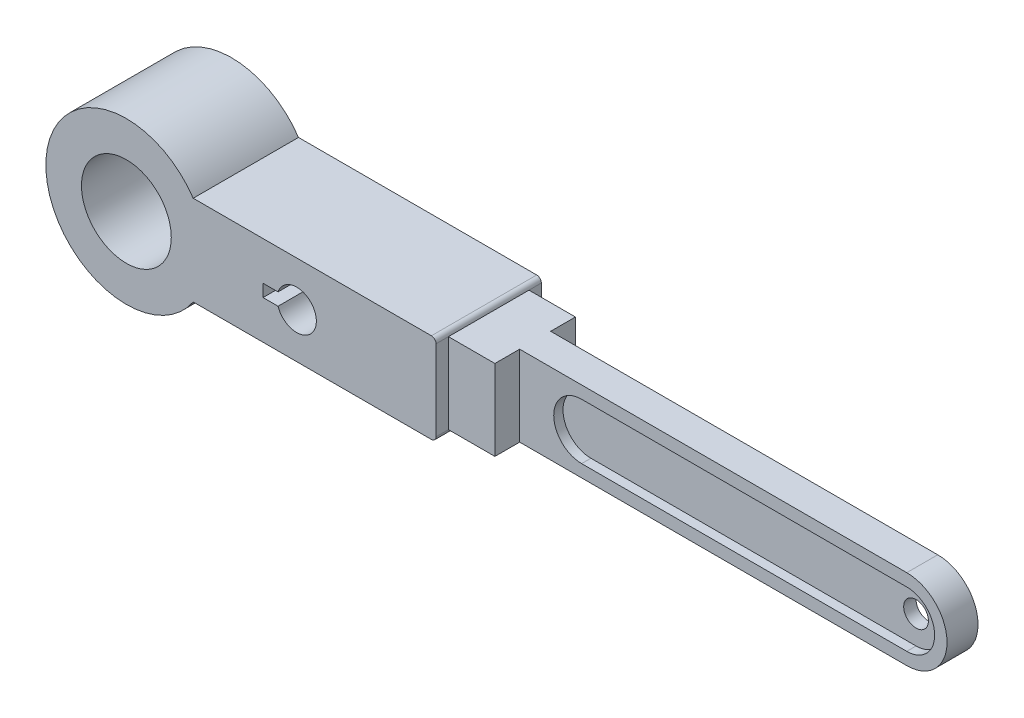
SolidWorks part; units mm, degrees
note: The reader was unsure of these and kept them because the rebuilt part matched: shared geometry of "Esboço1<4>", "Esboço1<8>", "Esboço1<9>".
ref_plane "Plano frontal" through (0, 0, 0) normal (0, 0, 1) x (1, 0, 0)
ref_plane "Plano superior" through (0, 0, 0) normal (0, 1, 0) x (1, 0, 0)
ref_plane "Plano direito" through (0, 0, 0) normal (1, 0, 0) x (0, 0, -1)
sketch "Esboço1" plane through (0, 0, 0) normal (0, 0, 1) x (1, 0, 0)
  line L0 (-116.3774, 0) -> (-67.7241, 0) construction
  line L3 (-116.3774, 0) -> (-67.7241, 0) construction
  line L4 (-93.8574, 14.5) -> (-17.8774, 14.5)
  line L6 (-93.8574, -14.5) -> (-17.8774, -14.5)
  line L7 (123.6199, 0) -> (18.6199, 0) construction
  line L8 (123.6199, -9) -> (18.6199, -9)
  line L9 (123.6199, 9) -> (18.6199, 9)
  line L10 (-16.3774, 13) -> (-16.3774, -13)
  line L11 (-93.8574, 14.5) -> (-94.7962, 14.5)
  line L12 (-93.8574, -14.5) -> (-94.7962, -14.5)
  line L13 (-1.3774, 13) -> (-16.3774, 13)
  line L14 (-1.3774, -13) -> (-16.3774, -13)
  line L15 (-63.2049, 0) -> (123.6199, 0) construction
  line L16 (-67.4042, -2) -> (-72.2434, -2)
  line L18 (-67.4042, 2) -> (-72.2434, 2)
  line L19 (-72.2434, -2) -> (-72.2434, 2)
  line L20 (-1.3774, 13) -> (-1.3774, -13)
  line L21 (-142.3774, 0) -> (-140.7697, 9.0011) construction
  line L22 (-63.2049, 0) -> (123.6199, 0) construction
  line L23 (-142.3774, 2.2947) -> (-142.3774, -4.0844) construction
  line L24 (-1.3774, 13) -> (123.6199, 13)
  line L25 (123.6259, -13) -> (-1.3774, -13)
  circle A1 centre (-116.3774, 0) radius 14.5
  arc A5 (123.6259, -13) -> (123.6199, 13) centre (123.6199, 0) ccw
  arc A6 (-67.4042, -2) -> (-67.4042, 2) centre (-61.3774, 0) ccw
  arc A7 (123.6199, -9) -> (123.6199, 9) centre (123.6199, 0) ccw
  arc A8 (18.6199, 9) -> (18.6199, -9) centre (18.6199, 0) ccw
  circle A9 centre (123.6199, 0) radius 4
  arc A10 (-94.7962, 14.5) -> (-94.7962, -14.5) centre (-116.3774, 0) ccw
  arc A11 (-16.3774, 13) -> (-17.8774, 14.5) centre (-17.8774, 13) ccw
  arc A12 (-16.3774, -13) -> (-17.8774, -14.5) centre (-17.8774, -13) cw
  point P3 (3.6259, 0)
  point P6 (3.6259, 0)
  point P11 (71.1199, 0)
  point P29 (-16.3774, 14.5)
  point P32 (-16.3774, -14.5)
  point P33 (-67.7274, 0)
  dimension "D1" = 29
  dimension "D3" = 14.5
  dimension "D4" = 55
  dimension "D2" = 12.7
  dimension "D5" = 8
  dimension "D8" = 52
  dimension "D9" = 1.5
  dimension "D10" = 1.5
  dimension "D12" = 115
  dimension "D6" = 100
  dimension "D7" = 14.5
  dimension "D11" = 4
extrude "Ressalto-extrusão1" add sketch "Esboço1" along normal mid plane 34 contours A12 L10 A11 L4 L11 A10 L12 L6 A6 L16 L19 L18 A1
extrude "Ressalto-extrusão2" add sketch "Esboço1<4>" along normal mid plane 26
sketch "Esboço1<4>" plane through (0, 0, 0) normal (0, 0, 1) x (1, 0, 0) same geometry as "Esboço1"
extrude "Ressalto-extrusão3" add sketch "Esboço1<8>" along normal mid plane 10 contours L25 A5 L24 L20 A8 L9 A7 L8
sketch "Esboço1<8>" plane through (0, 0, 0) normal (0, 0, 1) x (1, 0, 0) same geometry as "Esboço1"
extrude "Ressalto-extrusão4" add sketch "Esboço1<9>" along normal mid plane 4 contours L9 A8 L8 A7 A9
sketch "Esboço1<9>" plane through (0, 0, 0) normal (0, 0, 1) x (1, 0, 0) same geometry as "Esboço1"
